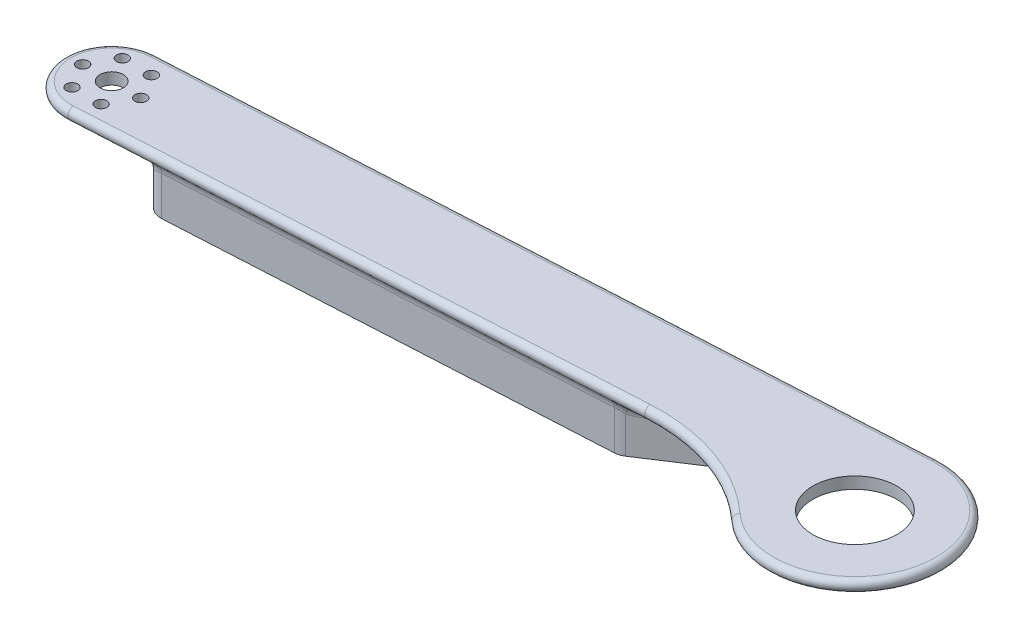
SolidWorks part; units mm, degrees
material "ABS"
ref_plane "Front Plane" through (0, 0, 0) normal (0, 0, 1) x (1, 0, 0)
ref_plane "Top Plane" through (0, 0, 0) normal (0, 1, 0) x (1, 0, 0)
ref_plane "Right Plane" through (0, 0, 0) normal (1, 0, 0) x (0, 0, -1)
ref_axis "Axis1" through (0, 55, 0) along (0, -1, 0)
sketch "Sketch2" plane through (0, 0, 0) normal (0, 1, 0) x (1, 0, 0)
  line L0 (-203.8945, 12.681) -> (-1.3022, 23.7769)
  line L1 (-1.3022, 23.7769) -> (0, 0) construction
  line L2 (-203.8945, 12.681) -> (-202.5055, -12.681) construction
  line L3 (-202.5055, -12.681) -> (-52.9616, -4.4906)
  circle A0 centre (-203.2, 0) radius 12.7 construction
  circle A1 centre (0, 0) radius 23.8125 construction
  circle A2 centre (-0.6077, 11.0959) radius 12.7 construction
  arc A3 (-203.8945, 12.681) -> (-202.5055, -12.681) centre (-203.2, 0) ccw
  arc A5 (-1.3022, 23.7769) -> (-16.016, -17.6217) centre (0, 0) cw
  circle A6 centre (0, 0) radius 11.5
  arc A7 (-52.9616, -4.4906) -> (-16.016, -17.6217) centre (-50.1835, -55.2145) cw
  dimension "D1" = 25.4
  dimension "D2" = 47.625
  dimension "D3" = 23
  dimension "D4" = 50.8
extrude "Boss-Extrude1" add sketch "Sketch2" along normal mid plane 3.175
sketch "Sketch5" plane through (0, 0, 0) normal (0, 1, 0) x (1, 0, 0)
  line L0 (0, 0) -> (0, 15.875) construction
  circle A0 centre (0, 15.875) radius 1.5875
  dimension "D1" = 3.175
  dimension "D2" = 15.875
extrude "Cut-Extrude3" [suppressed] cut sketch "Sketch5" against normal through all both and the other way through all
pattern_circular "CirPattern1" [suppressed] count 8 over 360 about axis through (0, 55, 0) along (0, -1, 0) of bodies 104
sketch "Sketch3" plane through (0, 0, 0) normal (0, 1, 0) x (1, 0, 0)
  line L0 (-34.1312, 0) -> (-23.8125, 0) construction
  line L2 (-190.5, 0) -> (-180.1812, 0) construction
  circle A1 centre (-34.1312, 0) radius 1.5875
  circle A2 centre (-180.1812, 0) radius 1.5875
  circle A3 centre (-165.5762, 0) radius 1.5875
  circle A4 centre (-150.9712, 0) radius 1.5875
  circle A5 centre (-136.3663, 0) radius 1.5875
  circle A6 centre (-121.7612, 0) radius 1.5875
  circle A7 centre (-107.1562, 0) radius 1.5875
  circle A8 centre (-92.5512, 0) radius 1.5875
  circle A9 centre (-77.9462, 0) radius 1.5875
  circle A10 centre (-63.3413, 0) radius 1.5875
  circle A11 centre (-48.7363, 0) radius 1.5875
  arc A12 (-203.8945, 12.681) -> (-202.5055, -12.681) centre (-203.2, 0) ccw construction
  arc A14 (-16.016, -17.6217) -> (-1.3022, 23.7769) centre (0, 0) ccw construction
  dimension "D2" = 3.175
  dimension "D1" = 146.05
  dimension "D3" = 11
extrude "Cut-Extrude1" [suppressed] cut sketch "Sketch3" against normal through all both and the other way through all
sketch "Sketch4" plane through (0, 0, 0) normal (0, -1, 0) x (1, 0, 0)
  line L0 (-203.2, 0) -> (-195.2625, 0) construction
  circle A0 centre (-203.2, 0) radius 3.175
  circle A1 centre (-195.2625, 0) radius 1.5875
  dimension "D1" = 6.35
  dimension "D2" = 3.175
  dimension "D3" = 7.9375
extrude "Cut-Extrude2" cut sketch "Sketch4" against normal through all both and the other way through all
pattern_circular "CirPattern2" count 6 over 360 about axis through (-203.2, 1.5875, 0) along (0, -1, 0) of "Cut-Extrude2" reverse direction yes
fillet "Fillet1" 2 edges at (22.4375, 1.5875, 7.9747) (22.4375, -1.5875, 7.9747) type full round first side face at (-211.1375, 1.5875, 1.5875) second side face at (-211.1375, -1.5875, 1.5875) middle face at (6.8892, 0, 2.4485)
sketch "Sketch6" plane through (0, -1.5875, 0) normal (0, -1, 0) x (-1, 0, 0)
  line L0 (31.7025, -1.7363) -> (32.9179, 20.4554) construction
  line L1 (31.7025, -1.7363) -> (187.1424, -10.2497) construction
  line L2 (32.9179, 20.4554) -> (188.3578, 11.9421)
  line L3 (187.1424, -10.2497) -> (188.3578, 11.9421) construction
  line L4 (31.7025, -1.7363) -> (188.3578, 11.9421) construction
  line L5 (32.9179, 20.4554) -> (187.1424, -10.2497) construction
  line L6 (203.8077, 11.0959) -> (1.2154, 22.1917) construction
  line L7 (53.0484, -2.9054) -> (202.5923, -11.0959) construction
  line L8 (23.8555, 20.9518) -> (32.9179, 20.4554)
  line L9 (187.1424, -10.2497) -> (61.0773, -3.3452)
  line L10 (61.0773, -3.3452) -> (23.8555, 20.9518)
  arc A1 (23.8555, 20.9518) -> (31.7025, -1.7363) centre (0, 0) cw construction
  arc A2 (188.3578, 11.9421) -> (187.1424, -10.2497) centre (203.2, 0) ccw
  point P1 (110.0302, 5.1029)
  dimension "D2" = 31.75
  dimension "D1" = 19.05
  dimension "D3" = 30
extrude "Boss-Extrude2" add sketch "Sketch6" along normal blind 12.7
fillet "Fillet2" radius 4.7625 4 edges at (-188.3578, -7.9375, -11.9421) (-23.8555, -7.9375, -20.9518) (-61.0773, -7.9375, 3.3452) (-187.1424, -7.9375, 10.2497)
fillet "Fillet3" radius 3.175 8 edges at (-183.5636, -1.5875, 8.1722) (-121.014, -1.5875, 6.6279) (-61.1296, -1.5875, 3.1855) (-49.3739, -1.5875, -4.2943) (-36.8164, -1.5875, -16.7067) (-111.2473, -1.5875, -16.1654) (-184.5735, -1.5875, -10.2678) (-184.1785, -1.5875, -1.0418)
